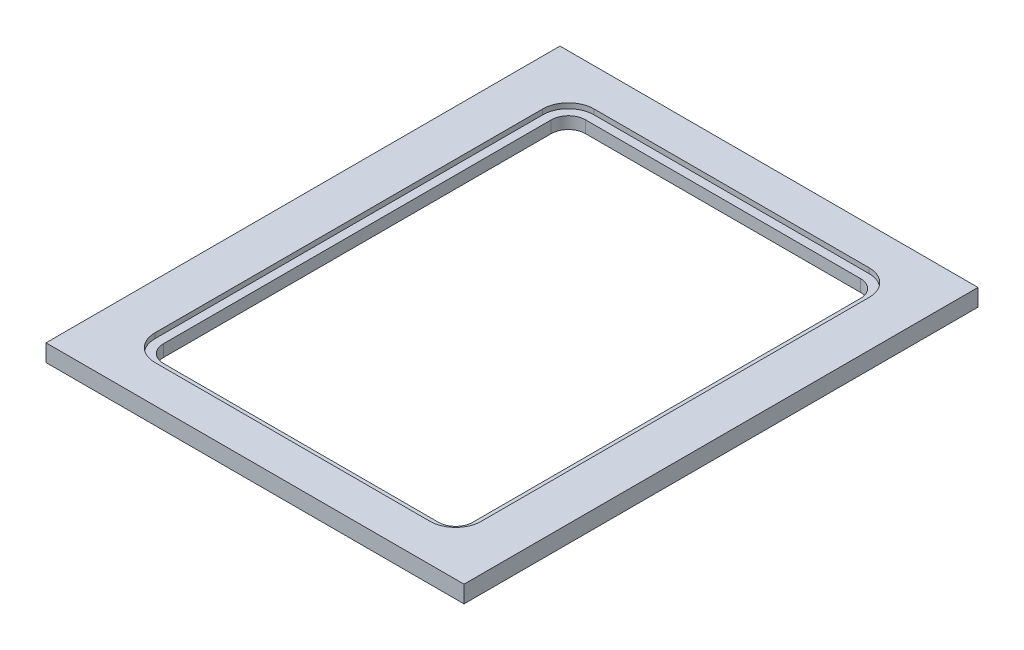
SolidWorks part; units mm, degrees
ref_plane "前视基准面" through (0, 0, 0) normal (0, 0, 1) x (1, 0, 0)
ref_plane "上视基准面" through (0, 0, 0) normal (0, 1, 0) x (1, 0, 0)
ref_plane "右视基准面" through (0, 0, 0) normal (1, 0, 0) x (0, 0, -1)
sketch "草图1" plane through (0, 0, 0) normal (0, 1, 0) x (1, 0, 0)
  line L0 (122, 0) -> (122, -300) construction
  line L1 (0, 0) -> (244, 0)
  line L2 (0, 0) -> (0, -300)
  line L3 (0, -300) -> (244, -300)
  line L4 (244, 0) -> (244, -300)
  line L5 (31.7339, -26.828) -> (212.2661, -26.828)
  line L6 (31.7339, -26.828) -> (31.7339, -273.172)
  line L7 (31.7339, -273.172) -> (212.2661, -273.172)
  line L8 (212.2661, -26.828) -> (212.2661, -273.172)
  line L9 (0, -150) -> (244, -150) construction
  dimension "D1" = 244
  dimension "D2" = 300
extrude "凸台-拉伸1" add sketch "草图1" along normal blind 10
fillet "圆角1" radius 10 4 edges at (31.7339, 5, 273.172) (212.2661, 5, 273.172) (31.7339, 5, 26.828) (212.2661, 5, 26.828)
sketch "草图2" plane through (0, 10, 0) normal (0, 1, 0) x (1, 0, 0)
  line L16 (202.2661, -21.828) -> (41.7339, -21.828)
  line L17 (26.7339, -36.828) -> (26.7339, -263.172)
  line L18 (41.7339, -278.172) -> (202.2661, -278.172)
  line L19 (217.2661, -263.172) -> (217.2661, -36.828)
  arc A8 (217.2661, -36.828) -> (202.2661, -21.828) centre (202.2661, -36.828) ccw
  arc A9 (41.7339, -21.828) -> (26.7339, -36.828) centre (41.7339, -36.828) ccw
  arc A10 (26.7339, -263.172) -> (41.7339, -278.172) centre (41.7339, -263.172) ccw
  arc A11 (202.2661, -278.172) -> (217.2661, -263.172) centre (202.2661, -263.172) ccw
extrude "切除-拉伸2" cut sketch "草图2" against normal blind 3
